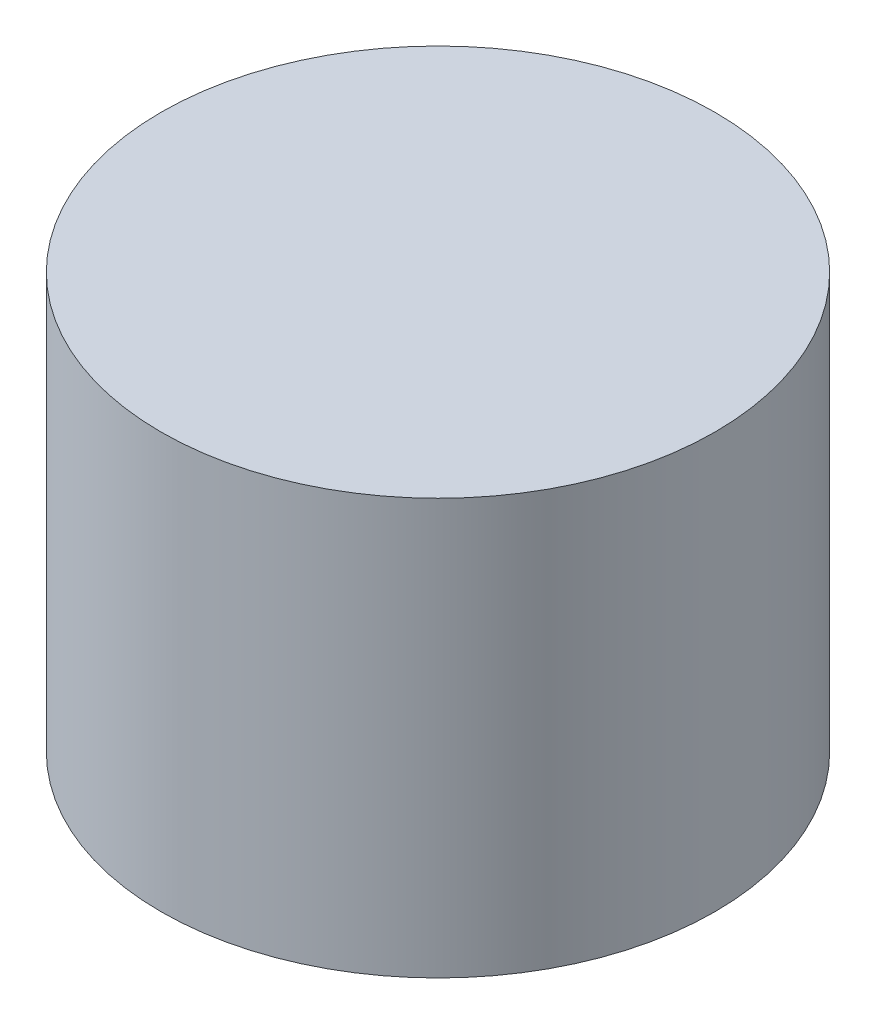
SolidWorks part; units mm, degrees
ref_plane "Front Plane" through (0, 0, 0) normal (0, 0, 1) x (1, 0, 0)
ref_plane "Top Plane" through (0, 0, 0) normal (0, 1, 0) x (1, 0, 0)
ref_plane "Right Plane" through (0, 0, 0) normal (1, 0, 0) x (0, 0, -1)
ref_axis "Axis1" through (0, 0, 0) along (0, 1, 0)
sketch "Sketch1" plane through (0, 0, 0) normal (0, 1, 0) x (1, 0, 0)
  circle A0 centre (0, 0) radius 2
  dimension "D1" = 4
extrude "Boss-Extrude1" add sketch "Sketch1" along normal blind 3
